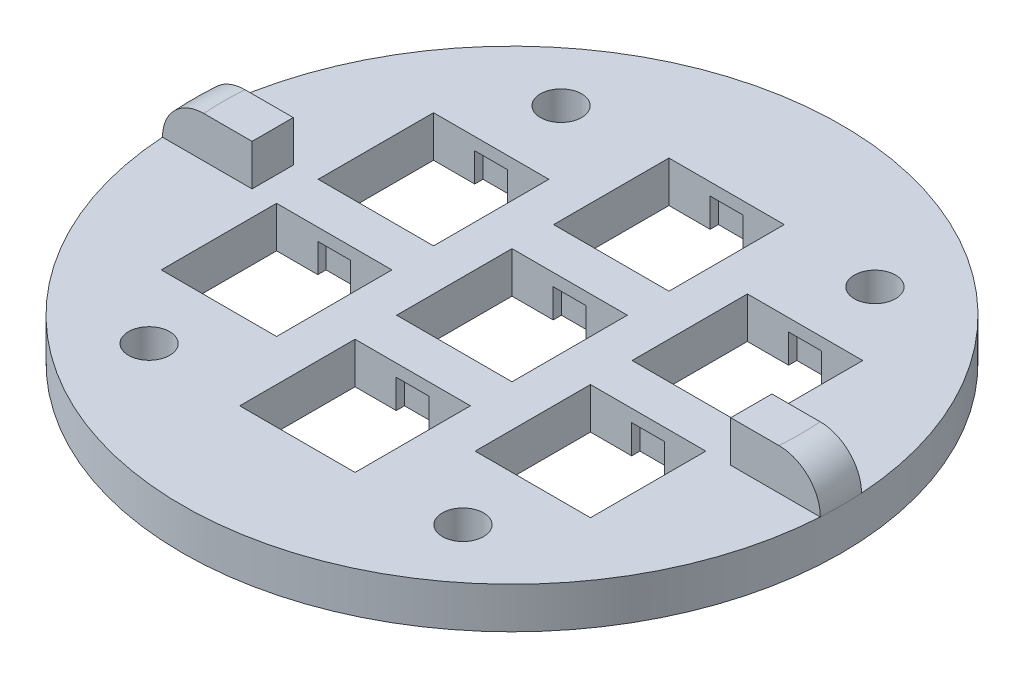
SolidWorks part; units mm, degrees
ref_plane "Front Plane" through (0, 0, 0) normal (0, 0, 1) x (1, 0, 0)
ref_plane "Top Plane" through (0, 0, 0) normal (0, 1, 0) x (1, 0, 0)
ref_plane "Right Plane" through (0, 0, 0) normal (1, 0, 0) x (0, 0, -1)
sketch "Sketch1" plane through (0, 0, 0) normal (0, 1, 0) x (1, 0, 0)
  line L5 (-7, 26.05) -> (-7, 12.05)
  line L6 (-7, 7) -> (7, 7)
  line L48 (-7, 7) -> (-7, -7)
  line L49 (-7, -7) -> (7, -7)
  line L50 (7, 7) -> (7, -7)
  line L51 (-7, 7) -> (7, -7) construction
  line L52 (-7, -7) -> (7, 7) construction
  line L53 (-7, 26.05) -> (7, 26.05)
  line L54 (7, 26.05) -> (7, 12.05)
  line L55 (-7, 12.05) -> (7, 12.05)
  line L56 (-7, -12.05) -> (-7, -26.05)
  line L57 (-7, -12.05) -> (7, -12.05)
  line L58 (7, -12.05) -> (7, -26.05)
  line L59 (-7, -26.05) -> (7, -26.05)
  line L60 (-26.05, 16.525) -> (-26.05, 2.525)
  line L61 (12.05, 16.525) -> (26.05, 16.525)
  line L62 (12.05, 16.525) -> (12.05, 2.525)
  line L63 (12.05, 2.525) -> (26.05, 2.525)
  line L64 (26.05, 16.525) -> (26.05, 2.525)
  line L65 (-26.05, 16.525) -> (-12.05, 16.525)
  line L66 (-12.05, 16.525) -> (-12.05, 2.525)
  line L67 (-26.05, 2.525) -> (-12.05, 2.525)
  line L68 (-26.05, -2.525) -> (-26.05, -16.525)
  line L69 (-26.05, -2.525) -> (-12.05, -2.525)
  line L70 (-12.05, -2.525) -> (-12.05, -16.525)
  line L71 (-26.05, -16.525) -> (-12.05, -16.525)
  line L72 (12.05, -2.525) -> (12.05, -16.525)
  line L73 (12.05, -2.525) -> (26.05, -2.525)
  line L74 (26.05, -2.525) -> (26.05, -16.525)
  line L75 (12.05, -16.525) -> (26.05, -16.525)
  circle A0 centre (0, 0) radius 40
  circle A1 centre (-19.05, 25) radius 2.5
  circle A2 centre (19.05, 25) radius 2.5
  circle A3 centre (19.05, -25) radius 2.5
  circle A4 centre (-19.05, -25) radius 2.5
  point P0 (0, 0)
  point P18 (-7, 0)
  dimension "D16" = 80
  dimension "D19" = 5
  dimension "D1" = 14
  dimension "D2" = 14
  dimension "D5" = 2
  dimension "D6" = 5.05
  dimension "D7" = 14
  dimension "D8" = 14
  dimension "D11" = 5.05
  dimension "D12" = 5.05
  dimension "D13" = 5.05
  dimension "D14" = 2.525
  dimension "D15" = 5.05
  dimension "D17" = 19.05
  dimension "D18" = 25
  dimension "D20" = 38.1
  dimension "D21" = 50
  dimension "D22" = 19.05
  dimension "D4" = 5.05
  dimension "D3" = 2
  dimension "D9" = 2
  dimension "D10" = 2
extrude "Boss-Extrude1" add sketch "Sketch1" along normal blind 5
sketch "Sketch2" plane through (0, 5, 0) normal (0, 1, 0) x (1, 0, 0)
  line L0 (-39.9218, 2.5) -> (-29.05, 2.5)
  line L1 (-39.9218, -2.5) -> (-29.05, -2.5)
  line L2 (-29.05, 2.5) -> (-29.05, -2.5)
  line L3 (29.05, 2.5) -> (29.05, -2.5)
  line L4 (-26.05, 16.525) -> (-26.05, 2.525) construction
  line L5 (26.05, 2.525) -> (26.05, 16.525) construction
  line L6 (29.05, -2.5) -> (39.9218, -2.5)
  line L7 (29.05, 2.5) -> (39.9218, 2.5)
  circle A0 centre (0, 0) radius 40 construction
  arc A1 (-39.9218, 2.5) -> (-39.9218, -2.5) centre (0, 0) ccw
  arc A2 (39.9218, 2.5) -> (39.9218, -2.5) centre (0, 0) cw
  dimension "D1" = 5
  dimension "D2" = 5
  dimension "D3" = 3
  dimension "D4" = 3
  dimension "D5" = 2.5
  dimension "D6" = 2.5
extrude "Boss-Extrude2" add sketch "Sketch2" along normal blind 5
fillet "Fillet1" radius 5 2 edges at (40, 10, 0) (-40, 10, 0)
sketch "Sketch3" plane through (0, 0, 0) normal (0, -1, 0) x (1, 0, 0)
  line L0 (-7, 26.05) -> (7, 26.05) construction
  line L1 (-2, 26.05) -> (2, 26.05)
  line L2 (-2, 26.05) -> (-2, 27.05)
  line L3 (-2, 27.05) -> (2, 27.05)
  line L4 (2, 26.05) -> (2, 27.05)
  line L5 (7, 12.05) -> (-7, 12.05) construction
  line L6 (-2, 12.05) -> (2, 12.05)
  line L7 (-2, 12.05) -> (-2, 11.05)
  line L8 (-2, 11.05) -> (2, 11.05)
  line L9 (2, 12.05) -> (2, 11.05)
  line L10 (-7, 12.05) -> (-7, 26.05) construction
  line L11 (-2, 7) -> (-2, 8)
  line L12 (-2, 7) -> (2, 7)
  line L13 (2, 7) -> (2, 8)
  line L14 (-2, 8) -> (2, 8)
  line L15 (-2, -7) -> (-2, -8)
  line L16 (-2, -7) -> (2, -7)
  line L17 (2, -7) -> (2, -8)
  line L18 (-2, -8) -> (2, -8)
  line L19 (-2, -12.05) -> (-2, -11.05)
  line L20 (-2, -12.05) -> (2, -12.05)
  line L21 (2, -12.05) -> (2, -11.05)
  line L22 (-2, -11.05) -> (2, -11.05)
  line L23 (-2, -26.05) -> (-2, -27.05)
  line L24 (-2, -26.05) -> (2, -26.05)
  line L25 (2, -26.05) -> (2, -27.05)
  line L26 (-2, -27.05) -> (2, -27.05)
  line L27 (-26.05, 16.525) -> (-12.05, 16.525) construction
  line L28 (-21.05, 16.525) -> (-17.05, 16.525)
  line L29 (-21.05, 16.525) -> (-21.05, 17.525)
  line L30 (-21.05, 17.525) -> (-17.05, 17.525)
  line L31 (-17.05, 16.525) -> (-17.05, 17.525)
  line L32 (-12.05, 2.525) -> (-26.05, 2.525) construction
  line L33 (-21.05, 2.525) -> (-17.05, 2.525)
  line L34 (-21.05, 2.525) -> (-21.05, 1.525)
  line L35 (-21.05, 1.525) -> (-17.05, 1.525)
  line L36 (-17.05, 2.525) -> (-17.05, 1.525)
  line L37 (-26.05, 2.525) -> (-26.05, 16.525) construction
  line L38 (17.05, 2.525) -> (17.05, 1.525)
  line L39 (17.05, 2.525) -> (21.05, 2.525)
  line L40 (21.05, 2.525) -> (21.05, 1.525)
  line L41 (17.05, 1.525) -> (21.05, 1.525)
  line L42 (17.05, 16.525) -> (17.05, 17.525)
  line L43 (17.05, 16.525) -> (21.05, 16.525)
  line L44 (21.05, 16.525) -> (21.05, 17.525)
  line L45 (17.05, 17.525) -> (21.05, 17.525)
  line L46 (17.05, -16.525) -> (17.05, -17.525)
  line L47 (17.05, -16.525) -> (21.05, -16.525)
  line L48 (21.05, -16.525) -> (21.05, -17.525)
  line L49 (17.05, -17.525) -> (21.05, -17.525)
  line L50 (17.05, -2.525) -> (17.05, -1.525)
  line L51 (17.05, -2.525) -> (21.05, -2.525)
  line L52 (21.05, -2.525) -> (21.05, -1.525)
  line L53 (17.05, -1.525) -> (21.05, -1.525)
  line L54 (-21.05, -16.525) -> (-21.05, -17.525)
  line L55 (-21.05, -16.525) -> (-17.05, -16.525)
  line L56 (-17.05, -16.525) -> (-17.05, -17.525)
  line L57 (-21.05, -17.525) -> (-17.05, -17.525)
  line L58 (-21.05, -2.525) -> (-21.05, -1.525)
  line L59 (-21.05, -2.525) -> (-17.05, -2.525)
  line L60 (-17.05, -2.525) -> (-17.05, -1.525)
  line L61 (-21.05, -1.525) -> (-17.05, -1.525)
  point P12 (0, 27.05)
  point P15 (0, 12.05)
  point P44 (-19.05, 16.525)
  point P47 (-19.05, 2.525)
  dimension "D1" = 4
  dimension "D2" = 1
  dimension "D3" = 1
  dimension "D4" = 4
  dimension "D5" = 7
  dimension "D6" = 7
  dimension "D7" = 4
  dimension "D8" = 4
  dimension "D9" = 1
  dimension "D10" = 1
  dimension "D11" = 7
  dimension "D12" = 7
extrude "Cut-Extrude1" cut sketch "Sketch3" against normal blind 3.5
